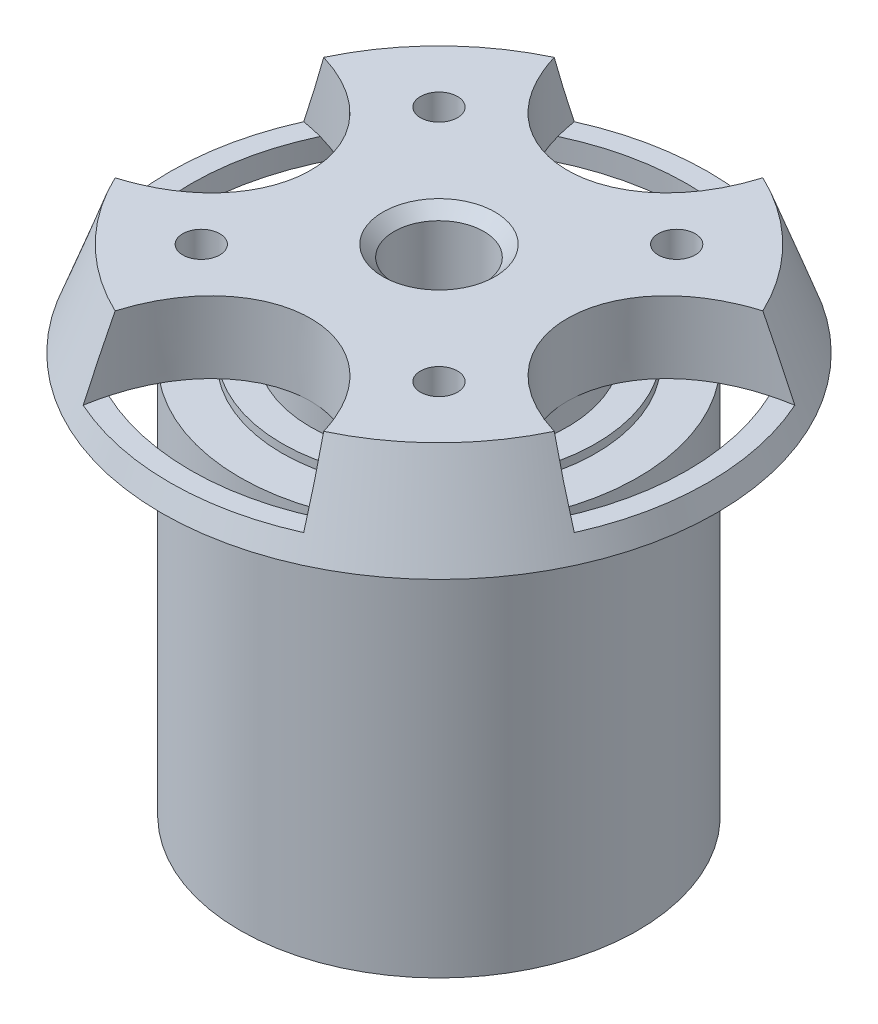
SolidWorks part; units mm, degrees
ref_plane "Front Plane" through (0, 0, 0) normal (0, 0, 1) x (1, 0, 0)
ref_plane "Top Plane" through (0, 0, 0) normal (0, 1, 0) x (1, 0, 0)
ref_plane "Right Plane" through (0, 0, 0) normal (1, 0, 0) x (0, 0, -1)
ref_axis "Axis1" through (0, 46.5537, 0) along (0, -1, 0)
sketch "Sketch2" plane through (0, 0, 0) normal (0, 0, 1) x (1, 0, 0)
  line L1 (0, 27.2574) -> (4, 27.2574)
  line L3 (4, 0) -> (21.6927, 0)
  line L4 (21.6927, 0) -> (24.75, -8.4)
  line L5 (24.75, -8.4) -> (14, -8.4)
  line L6 (14, -8.4) -> (14, -9.15)
  line L7 (14, -9.15) -> (17.75, -9.15)
  line L15 (17.75, -9.15) -> (17.75, -44.15)
  line L16 (17.75, -44.15) -> (4, -44.15)
  line L17 (4, -44.15) -> (4, 0)
  dimension "D3" = 0.75
  dimension "D5" = 4
  dimension "D7" = 8.4
  dimension "D9" = 27.2574
  dimension "D1" = 35
  dimension "D2" = 4
  dimension "D4" = 7
  dimension "D6" = 24.75
  dimension "D8" = 20
  dimension "D10" = 10
revolve "Revolve1" add sketch "Sketch2" angle 360 about axis through (0, 46.5537, 0) along (0, -1, 0) region at (11.5377, -20.8967, 0)
hole_wizard "Tap Drill for M4x0.7 Tap1" positions "Sketch3" profile "Sketch4" hole size "M4x0.7" standard "ANSI Metric"
sketch "Sketch3" plane through (0, 0, 0) normal (0, 1, 0) x (1, 0, 0)
  line L1 (10.6066, 10.6066) -> (-10.6066, 10.6066)
  line L2 (10.6066, 10.6066) -> (10.6066, -10.6066)
  line L3 (10.6066, -10.6066) -> (-10.6066, -10.6066)
  line L4 (-10.6066, 10.6066) -> (-10.6066, -10.6066)
  line L5 (10.6066, 10.6066) -> (-10.6066, -10.6066) construction
  line L6 (10.6066, -10.6066) -> (-10.6066, 10.6066) construction
  point P0 (10.6066, -10.6066)
  point P2 (-10.6066, -10.6066)
  point P4 (-10.6066, 10.6066)
  point P6 (10.6066, 10.6066)
  point P62 (0, 0)
  dimension "D1" = 30
sketch "Sketch4" plane through (10.6066, 0, 10.6066) normal (1, 0, 0) x (0, 0, 1)
  line L0 (0, 0) -> (0, 8.9914)
  line L1 (0, 8.9914) -> (1.65, 8)
  line L2 (1.65, 8) -> (1.65, 0)
  line L5 (1.65, 0) -> (0, 0)
  line L10 (0, 8.9914) -> (-1.65, 8) construction
  line L11 (0, -6.35) -> (0, 107.95) construction
  dimension "Hole Dia." = 3.3
  dimension "Hole Depth" = 8
  dimension "Drill Angle" = 118
chamfer "Chamfer1" distance 1 angle 45 1 edges at (0, 0, 4)
sketch "Sketch5" plane through (0, -8.4, 0) normal (0, -1, 0) x (1, 0, 0)
  line L0 (0, 0) -> (0, 24.75) construction
  line L2 (9.95, 22.6619) -> (-9.95, 22.6619)
  circle A0 centre (0, 0) radius 24.75
  circle A1 centre (0, 0) radius 24.75 construction
  spline S0 degree 3 poles (9.95, 22.6619) (8.05, 7.7127) (-8.05, 7.7127) (-9.95, 22.6619) knots 0 0 0 0 1 1 1 1
  point P10 (0, 22.6619)
  point P15 (0, 11.45)
  dimension "D3" = 27
  dimension "D1" = 13.3
  dimension "D2" = 19.9
ref_plane "Plane1" through (0, -6.4, 0) normal (0, -1, 0) x (-1, 0, 0)
sketch "Sketch8" plane through (0, -6.4, 0) normal (0, -1, 0) x (-1, 0, 0)
  circle A0 centre (0, 0) radius 24.75 construction
  arc A1 (-9.95, -22.6619) -> (9.95, -22.6619) centre (0, 0) ccw
  spline S0 degree 3 poles (1837.9023, -763.0428) (-1985.2905, 239.0843) (1985.3043, 239.0809) (-1837.9407, -763.0529) knots -3.593761 -3.593761 -3.593761 -3.593761 4.593788 4.593788 4.593788 4.593788 only from (-9.95, -22.6619) to (9.95, -22.6619) construction
  spline S1 degree 3 poles (-9.95, -22.6619) (-8.05, -7.7127) (8.05, -7.7127) (9.95, -22.6619) knots 0 0 0 0 1 1 1 1
extrude "Cut-Extrude3" cut sketch "Sketch8" against normal through all
pattern_circular "CirPattern2" count 4 every 90 about axis through (0, 46.5537, 0) along (0, -1, 0) of "Cut-Extrude3"
sketch "Sketch9" plane through (0, -6.4, 0) normal (0, 1, 0) x (1, 0, 0)
  circle A0 centre (0, 0) radius 22.15
  circle A1 centre (0, 0) radius 11.45
  spline S0 degree 3 poles (-21.9137, 9.8411) (-7.9621, 7.5479) (-7.9621, -7.5479) (-21.9137, -9.8411) knots 0.01697 0.01697 0.01697 0.01697 0.98303 0.98303 0.98303 0.98303 construction
  dimension "D1" = 44.3
extrude "Cut-Extrude5" cut sketch "Sketch9" against normal blind 2
equation "\"WHEEL_SHAFT_LEN\"=27.2574"
equation "\"D9@Sketch2\"=\"WHEEL_SHAFT_LEN\""
equation "\"ENCODER_SHAFT_LEN\"=9.88617"
